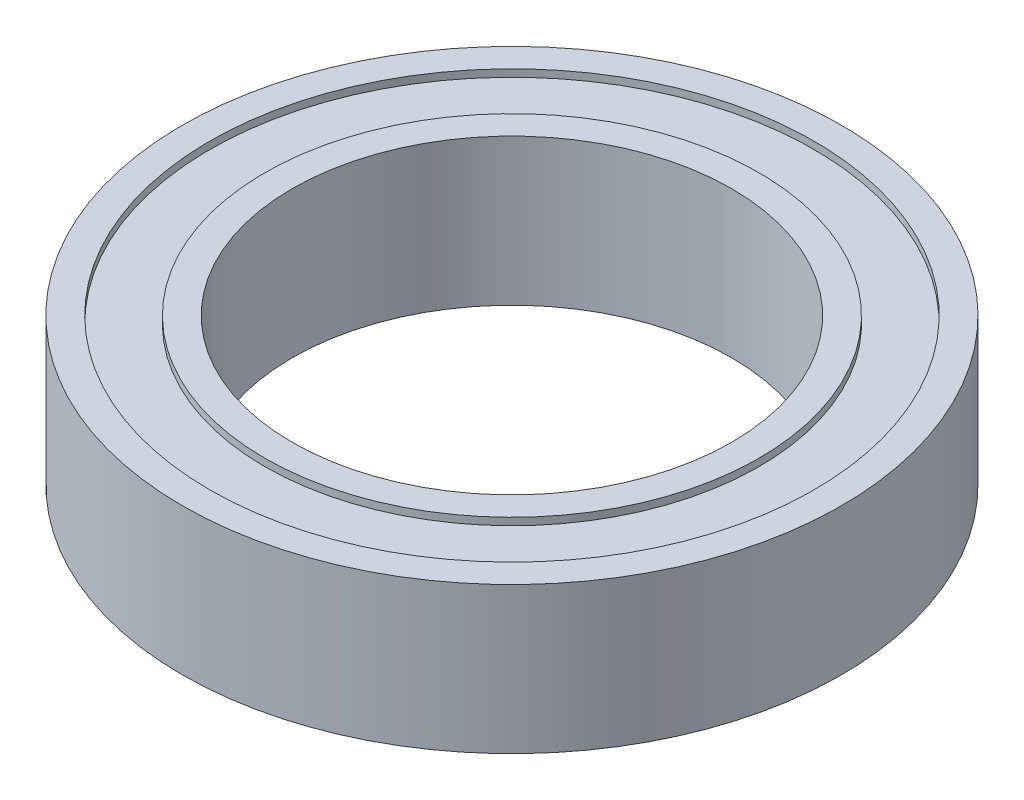
SolidWorks part; units mm, degrees
ref_plane "前视基准面" through (0, 0, 0) normal (0, 0, 1) x (1, 0, 0)
ref_plane "上视基准面" through (0, 0, 0) normal (0, 1, 0) x (1, 0, 0)
ref_plane "右视基准面" through (0, 0, 0) normal (1, 0, 0) x (0, 0, -1)
sketch "草图1" plane through (0, 0, 0) normal (0, 1, 0) x (1, 0, 0)
  circle A0 centre (0, 0) radius 6
  circle A1 centre (0, 0) radius 9
  dimension "D1" = 12
  dimension "D2" = 18
extrude "凸台-拉伸1" add sketch "草图1" along normal blind 2 and the other way blind 2
sketch "草图2" plane through (0, 2, 0) normal (0, 1, 0) x (1, 0, 0)
  circle A0 centre (0, 0) radius 6.75
  circle A1 centre (0, 0) radius 8.25
  dimension "D1" = 13.5
  dimension "D2" = 16.5
extrude "切除-拉伸1" cut sketch "草图2" against normal blind 0.2
mirror "镜向1" about plane through (0, 0, 0) normal (0, 1, 0) of "切除-拉伸1"
